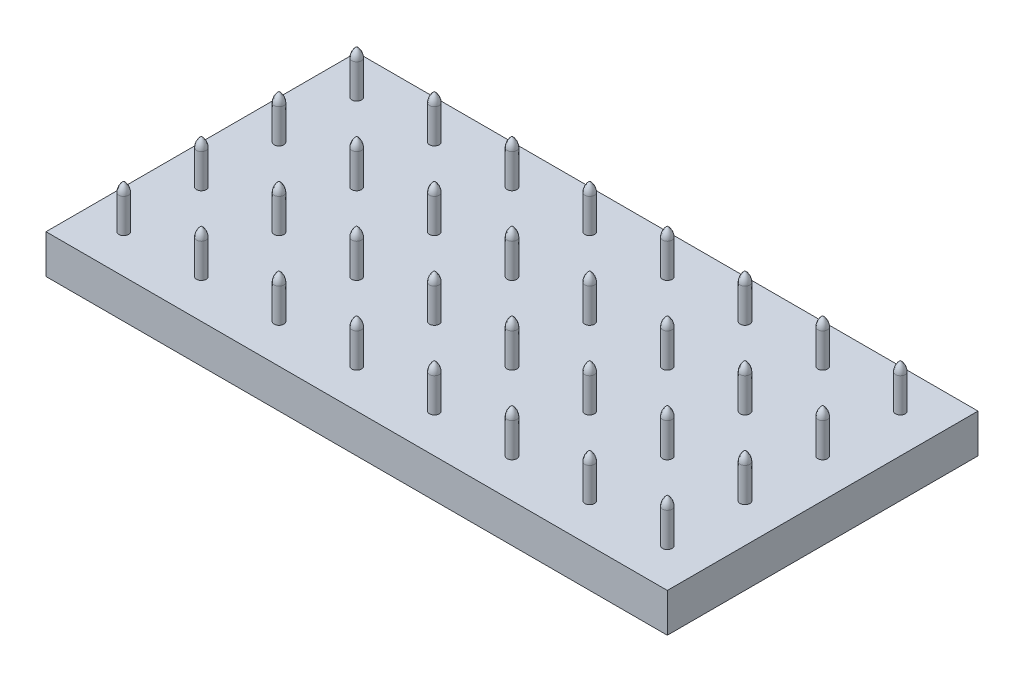
SolidWorks part; units mm, degrees
material "Silicon"
ref_plane "Front Plane" through (0, 0, 0) normal (0, 0, 1) x (1, 0, 0)
ref_plane "Top Plane" through (0, 0, 0) normal (0, 1, 0) x (1, 0, 0)
ref_plane "Right Plane" through (0, 0, 0) normal (1, 0, 0) x (0, 0, -1)
sketch "Sketch1" plane through (0, 0, 0) normal (0, 1, 0) x (1, 0, 0)
  line L1 (-50.8, -25.4) -> (50.8, -25.4)
  line L2 (-50.8, -25.4) -> (-50.8, 25.4)
  line L3 (-50.8, 25.4) -> (50.8, 25.4)
  line L4 (50.8, -25.4) -> (50.8, 25.4)
  line L5 (-50.8, -25.4) -> (50.8, 25.4) construction
  line L6 (-50.8, 25.4) -> (50.8, -25.4) construction
  point P0 (0, 0)
  dimension "D1" = 50.8
  dimension "D2" = 101.6
extrude "Boss-Extrude1" add sketch "Sketch1" along normal blind 6.35
sketch "Sketch3" plane through (0, 6.35, 0) normal (0, 1, 0) x (1, 0, 0)
  line L0 (-50.8, 25.4) -> (-44.45, 25.4) construction
  line L1 (50.8, 25.4) -> (-50.8, 25.4) construction
  line L2 (-44.45, 25.4) -> (-44.45, 19.05) construction
  line L3 (-44.45, 19.05) -> (-50.8, 19.05) construction
  line L4 (-50.8, 25.4) -> (-50.8, -25.4) construction
  line L5 (-50.8, 19.05) -> (-50.8, 25.4) construction
  dimension "D1" = 6.35
sketch "Sketch2" plane through (0, 6.35, 0) normal (0, 1, 0) x (1, 0, 0)
  line L0 (-44.45, 19.05) -> (-31.75, 19.05) construction
  circle A0 centre (-44.45, 19.05) radius 0.7937
  point P2 (0, 0)
  dimension "D3" = 12.7
extrude "Boss-Extrude2" add sketch "Sketch2" along normal blind 5.5563
ref_plane "Plane6" through (-44.45, 0, 0) normal (1, 0, 0) x (0, 0, -1)
sketch "Sketch12" plane through (-44.45, 0, 0) normal (1, 0, 0) x (0, 0, -1)
  line L0 (19.05, 6.35) -> (19.05, 11.9062) construction
  line L1 (19.05, 11.9062) -> (19.05, 13.4938)
  line L3 (19.05, 11.9062) -> (18.2563, 11.9062)
  arc A2 (19.05, 13.4938) -> (18.2563, 11.9062) centre (20.3259, 11.8636) ccw
revolve "Revolve1" add sketch "Sketch12" angle 360 about L0
pattern_linear "LPattern1" count 8 spacing 12.7 along (1, 0, 0) count 4 spacing 12.7 along (0, 0, 1) of "Boss-Extrude2", "Revolve1"
